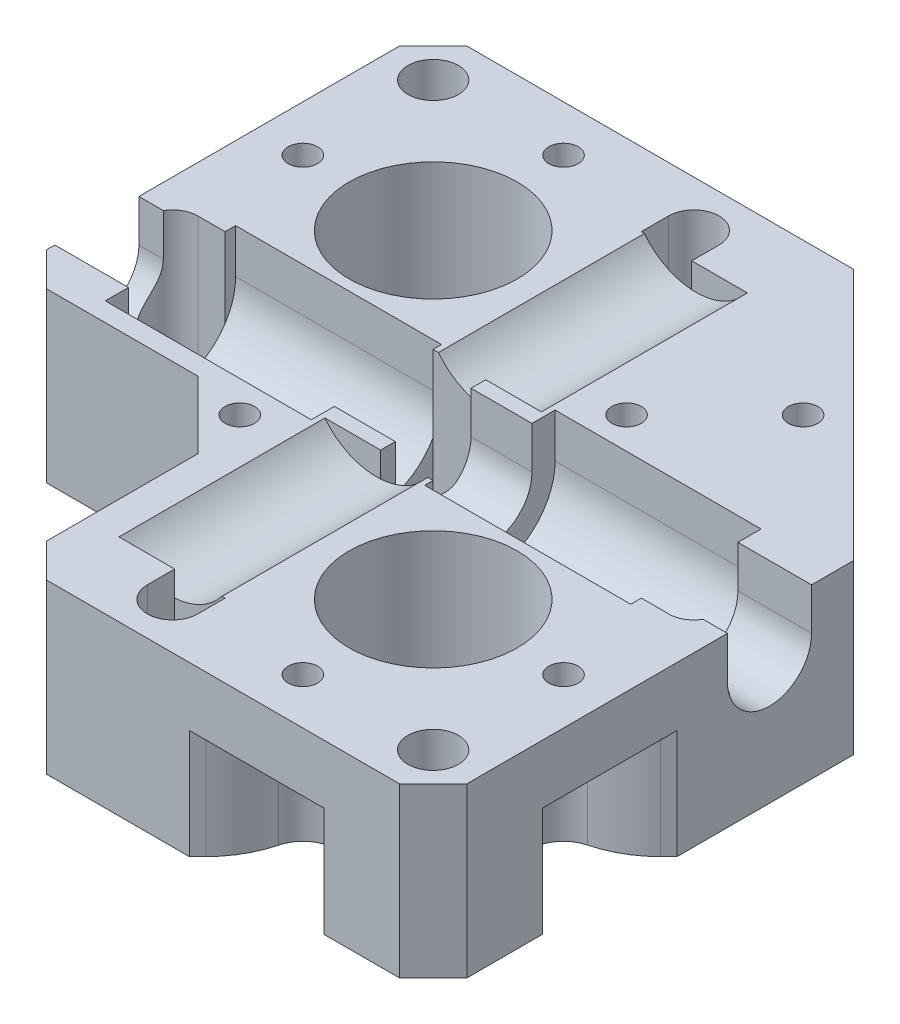
SolidWorks part; units mm, degrees
ref_plane "Front Plane" through (0, 0, 0) normal (0, 0, 1) x (1, 0, 0)
ref_plane "Top Plane" through (0, 0, 0) normal (0, 1, 0) x (1, 0, 0)
ref_plane "Right Plane" through (0, 0, 0) normal (1, 0, 0) x (0, 0, -1)
sketch "Sketch1" plane through (0, 0, 0) normal (0, 1, 0) x (1, 0, 0)
  line L1 (-40, -40) -> (40, -40)
  line L2 (-40, -40) -> (-40, 40)
  line L3 (-40, 40) -> (40, 40)
  line L4 (40, -40) -> (40, 40)
  line L5 (-40, -40) -> (40, 40) construction
  line L6 (-40, 40) -> (40, -40) construction
  point P0 (0, 0)
  dimension "D1" = 80
  dimension "D2" = 80
extrude "Boss-Extrude1" add sketch "Sketch1" against normal blind 20
sketch "Sketch2" plane through (0, 0, 0) normal (0, 1, 0) x (1, 0, 0)
  circle A0 centre (-11.5, -11.5) radius 1.75
  circle A1 centre (11.5, 11.5) radius 1.75
  circle A2 centre (22, 22) radius 1.75
  circle A3 centre (19, -34.5) radius 1.75
  circle A4 centre (34.5, -19) radius 1.75
  circle A5 centre (-34.5, 19) radius 1.75
  circle A6 centre (-19, 34.5) radius 1.75
  dimension "D1" = 3.5
  dimension "D2" = 3.5
  dimension "D3" = 3.5
  dimension "D4" = 3.5
  dimension "D5" = 3.5
  dimension "D6" = 3.5
  dimension "D7" = 3.5
  dimension "D8" = 11.5
  dimension "D9" = 11.5
  dimension "D10" = 11.5
  dimension "D11" = 11.5
  dimension "D12" = 22
  dimension "D13" = 22
  dimension "D14" = 34.5
  dimension "D15" = 34.5
  dimension "D16" = 19
  dimension "D17" = 19
  dimension "D18" = 34.5
  dimension "D19" = 19
  dimension "D20" = 19
  dimension "D21" = 34.5
extrude "Cut-Extrude1" cut sketch "Sketch2" against normal through all both and the other way through all
sketch "Sketch3" plane through (0, 0, 0) normal (0, 1, 0) x (1, 0, 0)
  line L1 (31.25, -7.75) -> (6.75, -7.75)
  line L2 (31.25, -7.75) -> (31.25, 7.75)
  line L3 (31.25, 7.75) -> (6.75, 7.75)
  line L4 (6.75, -7.75) -> (6.75, 7.75)
  line L5 (31.25, -7.75) -> (6.75, 7.75) construction
  line L6 (31.25, 7.75) -> (6.75, -7.75) construction
  line L7 (-6.75, -7.75) -> (-31.25, -7.75)
  line L8 (-6.75, -7.75) -> (-6.75, 7.75)
  line L9 (-6.75, 7.75) -> (-31.25, 7.75)
  line L10 (-31.25, -7.75) -> (-31.25, 7.75)
  line L11 (-6.75, -7.75) -> (-31.25, 7.75) construction
  line L12 (-6.75, 7.75) -> (-31.25, -7.75) construction
  point P0 (19, 0)
  point P5 (-19, 0)
  point P10 (0, 0)
  dimension "D1" = 15.5
  dimension "D2" = 0
  dimension "D3" = 24.5
  dimension "D4" = 19
  dimension "D5" = 24.5
  dimension "D6" = 15.5
  dimension "D7" = 0
  dimension "D8" = 19
extrude "Cut-Extrude2" cut sketch "Sketch3" against normal blind 13
fillet "Fillet1" radius 7.75 4 edges at (19, -13, 7.75) (19, -13, -7.75) (-19, -13, 7.75) (-19, -13, -7.75)
sketch "Sketch4" plane through (0, 0, 0) normal (0, 1, 0) x (1, 0, 0)
  line L1 (-7.75, -31.25) -> (7.75, -31.25)
  line L2 (-7.75, -31.25) -> (-7.75, -6.75)
  line L3 (-7.75, -6.75) -> (7.75, -6.75)
  line L4 (7.75, -31.25) -> (7.75, -6.75)
  line L5 (-7.75, -31.25) -> (7.75, -6.75) construction
  line L6 (-7.75, -6.75) -> (7.75, -31.25) construction
  line L7 (-7.75, 6.75) -> (7.75, 6.75)
  line L8 (-7.75, 6.75) -> (-7.75, 31.25)
  line L9 (-7.75, 31.25) -> (7.75, 31.25)
  line L10 (7.75, 6.75) -> (7.75, 31.25)
  point P0 (0, -19)
  dimension "D1" = 15.5
  dimension "D2" = 0
  dimension "D3" = 24.5
  dimension "D4" = 19
  dimension "D5" = 24.5
  dimension "D6" = 6.75
  dimension "D7" = 15.5
  dimension "D8" = 7.75
extrude "Cut-Extrude3" cut sketch "Sketch4" against normal blind 3
sketch3d "3DSketch1" [suppressed]
  line L1 (-8, -3, 8) -> (8, -3, 8)
  line L2 (-8, -3, 8) -> (-8, 0, 8)
  line L3 (-8, 0, 8) -> (8, 0, 8)
  line L4 (8, -3, 8) -> (8, 0, 8)
  circle A0 centre (0, 5, 8) radius 8
  point P2 (0, 5, 16)
  point P3 (0, 0, 8)
  point P5 (0, 0, 8)
  dimension "D4" = 16
  dimension "D1" = 8
  dimension "D2" = 0
  dimension "D3" = 5
sketch "Sketch5" plane through (0, 0, 31.25) normal (0, 0, -1) x (-1, 0, 0)
  line L0 (7.75, -3) -> (-7.75, -3) construction
  line L5 (7.75, 0) -> (-7.75, 0)
  line L6 (-7.75, 0) -> (-7.75, -3)
  line L7 (-7.75, -3) -> (7.75, -3)
  line L8 (7.75, -3) -> (7.75, 0)
  line L9 (7.75, 0) -> (-7.75, 0)
  line L10 (-7.75, 0) -> (-7.75, -3)
  line L11 (-7.75, -3) -> (7.75, -3)
  line L12 (7.75, -3) -> (7.75, 0)
  circle A0 centre (0, 4.75) radius 7.75
  line M6 (7.75, 0) -> (-7.75, 0)
  line M7 (-7.75, 0) -> (-7.75, -3)
  line M8 (-7.75, -3) -> (7.75, -3)
  line M9 (7.75, -3) -> (7.75, 0)
  dimension "D2" = 15.5
  dimension "D1" = 7.75
  dimension "D3" = 0
extrude "Boss-Extrude2" add sketch "Sketch5" along normal blind 23.5 contours A0 M6 M7 M8 | A0 L11 M9 M6 region at (-5.7238, -1.841, 31.25) region at (5.7238, -1.841, 31.25)
mirror "Mirror1" about plane through (0, 0, 0) normal (0, 0, 1) of "Boss-Extrude2"
sketch "Sketch6" plane through (0, 0, 0) normal (1, 0, 0) x (0, 0, -1)
  line L1 (5, -5) -> (-5, -5)
  line L2 (5, -5) -> (5, 0)
  line L3 (5, 0) -> (-5, 0)
  line L4 (-5, -5) -> (-5, 0)
  circle A0 centre (0, -5) radius 5
  dimension "D2" = 10
  dimension "D1" = 5
extrude "Cut-Extrude4" cut sketch "Sketch6" against normal through all both and the other way through all contours L1 A0 | A0 L3 L4 | A0 L2 L3 | L1 A0 region at (0, -7.1221, 0) region at (0, -1.1168, -3.8832) region at (0, -2.8779, 0) region at (0, -1.1168, 3.8832)
sketch "Sketch7" plane through (0, 0, 0) normal (0, 1, 0) x (1, 0, 0)
  circle A0 centre (19, -19) radius 10
  circle A1 centre (-19, 19) radius 10
  dimension "D5" = 20
  dimension "D6" = 20
  dimension "D1" = 19
  dimension "D2" = 19
  dimension "D3" = 19
  dimension "D4" = 19
extrude "Cut-Extrude5" cut sketch "Sketch7" against normal through all both and the other way through all
sketch "Sketch8" plane through (0, 0, -6.75) normal (0, 0, -1) x (-1, 0, 0)
  line L4 (6.75, 0) -> (-6.75, 0)
  line L5 (-6.75, 0) -> (-6.75, -3)
  line L6 (-6.75, -3) -> (6.75, -3)
  line L7 (6.75, -3) -> (6.75, 0)
  line L8 (6.75, 0) -> (-6.75, 0)
  line L9 (-6.75, 0) -> (-6.75, -3)
  line L10 (-6.75, -3) -> (6.75, -3)
  line L11 (6.75, -3) -> (6.75, 0)
  arc A0 (0, -3) -> (6.1237, 0) centre (0, 4.75) ccw construction
  arc A1 (-6.1237, 0) -> (0, -3) centre (0, 4.75) ccw construction
  arc A2 (0, -3) -> (6.1237, 0) centre (0, 4.75) ccw
  arc A3 (-6.1237, 0) -> (0, -3) centre (0, 4.75) ccw
  line M5 (6.75, 0) -> (-6.75, 0)
  line M6 (-6.75, 0) -> (-6.75, -3)
  line M7 (-6.75, -3) -> (6.75, -3)
  line M8 (6.75, -3) -> (6.75, 0)
  dimension "D1" = 0
extrude "Boss-Extrude3" add sketch "Sketch8" along normal blind 1.5 contours A3 M5 M6 M7 | A2 L10 M8 M5 region at (-5.1079, -1.9786, -6.75) region at (5.1079, -1.9786, -6.75)
mirror "Mirror2" about plane through (0, 0, 0) normal (0, 0, 1) of "Boss-Extrude3"
sketch "Sketch9" plane through (0, 0, 0) normal (0, 1, 0) x (1, 0, 0)
  line L0 (-10, -18) -> (-18, -10)
  line L1 (-40, -40) -> (-10, -40)
  line L2 (-40, -40) -> (-40, -10)
  line L3 (-40, -10) -> (-10, -10)
  line L4 (-10, -40) -> (-10, -10)
  line L5 (-10, -10) -> (-18, -10)
  line L6 (-10, -10) -> (-10, -18)
  line L7 (-10, -18) -> (-18, -18)
  line L8 (-18, -10) -> (-18, -18)
  dimension "D1" = 30
  dimension "D2" = 30
  dimension "D3" = 8
  dimension "D4" = 8
extrude "Cut-Extrude6" cut sketch "Sketch9" against normal through all both and the other way through all contours L0 L8 L7 | L8 L3 L2 L1 L4 L7 region at (-15.3333, 0, 15.3333) region at (-25.8421, 0, 25.8421)
chamfer "Chamfer1" distance 4 angle 45 4 edges at (40, -10, 40) (-40, -10, -40) (-40, -10, 10) (-10, -10, 40)
chamfer "Chamfer2" distance 30 angle 45 1 edges at (40, -10, -40)
sketch "Sketch10" plane through (0, 0, 0) normal (0, 1, 0) x (1, 0, 0)
  circle A0 centre (3.5, -3.5) radius 1.75
  circle A1 centre (-3.5, 3.5) radius 1.75
  circle A2 centre (34.5, -3.5) radius 1.75
  circle A3 centre (3.5, -34.5) radius 1.75
  circle A4 centre (34.5, -34.5) radius 1.75
  circle A5 centre (-3.5, 34.5) radius 1.75
  circle A6 centre (-34.5, 3.5) radius 1.75
  circle A7 centre (-34.5, 34.5) radius 1.75
  dimension "D5" = 3.5
  dimension "D6" = 3.5
  dimension "D8" = 3.5
  dimension "D10" = 3.5
  dimension "D11" = 3.5
  dimension "D12" = 3.5
  dimension "D13" = 3.5
  dimension "D16" = 3.5
  dimension "D1" = 3.5
  dimension "D2" = 3.5
  dimension "D3" = 3.5
  dimension "D4" = 3.5
  dimension "D7" = 31
  dimension "D9" = 31
  dimension "D14" = 31
  dimension "D15" = 31
extrude "Cut-Extrude7" cut sketch "Sketch10" against normal through all both and the other way through all
sketch "Sketch11" plane through (0, 0, 0) normal (0, 1, 0) x (1, 0, 0)
  line L0 (-6.75, 5) -> (-6.75, 7.75) construction
  line L1 (-0.5, 3.5) -> (-6.75, 3.5)
  line L2 (-0.5, 3.5) -> (-0.5, 6.375)
  line L3 (-0.5, 6.375) -> (-6.75, 6.375)
  line L4 (-6.75, 3.5) -> (-6.75, 6.375)
  line L5 (6.75, -5) -> (6.75, -7.75) construction
  line L6 (0.5, -3.5) -> (6.75, -3.5)
  line L7 (0.5, -3.5) -> (0.5, -6.375)
  line L8 (0.5, -6.375) -> (6.75, -6.375)
  line L9 (6.75, -3.5) -> (6.75, -6.375)
  line L10 (31.25, -7.75) -> (31.25, -5) construction
  line L11 (34.5, -0.5) -> (31.25, -0.5)
  line L12 (34.5, -0.5) -> (34.5, -6.375)
  line L13 (34.5, -6.375) -> (31.25, -6.375)
  line L14 (31.25, -0.5) -> (31.25, -6.375)
  line L15 (-6.1237, -31.25) -> (6.1237, -31.25) construction
  line L16 (-34.5, 6.5) -> (-31.25, 6.5)
  line L17 (-34.5, 6.5) -> (-34.5, 0.5)
  line L18 (-34.5, 0.5) -> (-31.25, 0.5)
  line L19 (-31.25, 6.5) -> (-31.25, 0.5)
  line L20 (3.5, -0.5) -> (6.75, -0.5)
  line L21 (3.5, -0.5) -> (3.5, -6.375)
  line L22 (3.5, -6.375) -> (6.75, -6.375)
  line L23 (6.75, -0.5) -> (6.75, -6.375)
  line L24 (-3.5, 0.5) -> (-6.75, 0.5)
  line L25 (-3.5, 0.5) -> (-3.5, 6.375)
  line L26 (-3.5, 6.375) -> (-6.75, 6.375)
  line L27 (-6.75, 0.5) -> (-6.75, 6.375)
  line L32 (0.5, -31.25) -> (6.5, -31.25)
  line L33 (0.5, -31.25) -> (0.5, -34.5)
  line L34 (0.5, -34.5) -> (6.5, -34.5)
  line L35 (6.5, -31.25) -> (6.5, -34.5)
  line L36 (-31.25, 7.75) -> (-31.25, 5) construction
  line L37 (-0.4632, 34.5) -> (-6.4632, 34.5)
  line L38 (-0.4632, 34.5) -> (-0.4632, 31.25)
  line L39 (-0.4632, 31.25) -> (-6.4632, 31.25)
  line L40 (-6.4632, 34.5) -> (-6.4632, 31.25)
  line L41 (6.1237, 31.25) -> (-6.1237, 31.25) construction
  circle A0 centre (-34.5, 3.5) radius 1.75 construction
  circle A1 centre (34.5, -3.5) radius 1.75 construction
  circle A2 centre (-3.5, 3.5) radius 1.75 construction
  circle A3 centre (3.5, -3.5) radius 1.75 construction
  circle A4 centre (-34.5, 3.5) radius 1.75
  circle A5 centre (34.5, -3.5) radius 1.75
  circle A6 centre (-3.5, 3.5) radius 1.75
  circle A7 centre (3.5, -3.5) radius 1.75
  circle A8 centre (-3.5, 3.5) radius 3
  circle A9 centre (3.5, -3.5) radius 3
  circle A10 centre (34.5, -3.5) radius 3
  circle A11 centre (-34.5, 3.5) radius 3
  circle A12 centre (-3.5, 34.5) radius 1.75 construction
  circle A13 centre (3.5, -34.5) radius 1.75 construction
  circle A14 centre (-3.5, 34.5) radius 1.75
  circle A15 centre (3.5, -34.5) radius 1.75
  circle A16 centre (3.5, -34.5) radius 3
  circle A17 centre (-3.5, 34.5) radius 3.0368
  dimension "D1" = 6
  dimension "D2" = 6
  dimension "D3" = 6
  dimension "D4" = 6
  dimension "D5" = 0
  dimension "D6" = 0
extrude "Cut-Extrude11" [suppressed] cut sketch "Sketch11" against normal blind 17 contours A17 | L40 L39 L38 L37 | L4 L1 L2 L3 | L26 L25 L24 L27 | A8 | A9 | L9 L6 L7 L8 | L22 L21 L20 L23 | L11 L14 L13 L12 | A10 | A11 | L16 L19 L18 L17 | A16 | L35 L34 L33 L32
sketch "Sketch12" plane through (0, 0, 0) normal (0, 1, 0) x (1, 0, 0)
  circle A0 centre (-34.5, 34.5) radius 1.75 construction
  circle A1 centre (34.5, -34.5) radius 1.75 construction
  circle A2 centre (-34.5, 34.5) radius 1.75
  circle A3 centre (34.5, -34.5) radius 1.75
  circle A4 centre (34.5, -34.5) radius 3
  circle A5 centre (-34.5, 34.5) radius 3
  dimension "D1" = 6
  dimension "D2" = 6
extrude "Cut-Extrude12" cut sketch "Sketch12" against normal blind 8
sketch "Sketch13" plane through (0, -20, 0) normal (0, -1, 0) x (1, 0, 0)
  circle A0 centre (-19, -19) radius 10 construction
  circle A1 centre (19, 19) radius 10 construction
  circle A2 centre (-19, -19) radius 10
  circle A3 centre (19, 19) radius 10
  circle A4 centre (19, 19) radius 11
  circle A5 centre (-19, -19) radius 11
  dimension "D1" = 22
  dimension "D2" = 22
extrude "Cut-Extrude13" cut sketch "Sketch13" against normal blind 3
sketch "Sketch14" plane through (0, -20, 0) normal (0, -1, 0) x (1, 0, 0)
  line L1 (-34.5, -15.8246) -> (-37.25, -17.4123)
  line L2 (-37.25, -17.4123) -> (-37.25, -20.5877)
  line L3 (-37.25, -20.5877) -> (-34.5, -22.1754)
  line L4 (-34.5, -22.1754) -> (-31.75, -20.5877)
  line L5 (-31.75, -20.5877) -> (-31.75, -17.4123)
  line L6 (-31.75, -17.4123) -> (-34.5, -15.8246)
  line L7 (-15.8246, -34.5) -> (-17.4123, -31.75)
  line L8 (-17.4123, -31.75) -> (-20.5877, -31.75)
  line L9 (-20.5877, -31.75) -> (-22.1754, -34.5)
  line L10 (-22.1754, -34.5) -> (-20.5877, -37.25)
  line L11 (-20.5877, -37.25) -> (-17.4123, -37.25)
  line L12 (-17.4123, -37.25) -> (-15.8246, -34.5)
  line L13 (34.5, 22.1754) -> (31.75, 20.5877)
  line L14 (31.75, 20.5877) -> (31.75, 17.4123)
  line L15 (31.75, 17.4123) -> (34.5, 15.8246)
  line L16 (34.5, 15.8246) -> (37.25, 17.4123)
  line L17 (37.25, 17.4123) -> (37.25, 20.5877)
  line L18 (37.25, 20.5877) -> (34.5, 22.1754)
  line L19 (22.1754, 34.5) -> (20.5877, 37.25)
  line L20 (20.5877, 37.25) -> (17.4123, 37.25)
  line L21 (17.4123, 37.25) -> (15.8246, 34.5)
  line L22 (15.8246, 34.5) -> (17.4123, 31.75)
  line L23 (17.4123, 31.75) -> (20.5877, 31.75)
  line L24 (20.5877, 31.75) -> (22.1754, 34.5)
  line L25 (-8.3246, 11.5) -> (-9.9123, 14.25)
  line L26 (-9.9123, 14.25) -> (-13.0877, 14.25)
  line L27 (-13.0877, 14.25) -> (-14.6754, 11.5)
  line L28 (-14.6754, 11.5) -> (-13.0877, 8.75)
  line L29 (-13.0877, 8.75) -> (-9.9123, 8.75)
  line L30 (-9.9123, 8.75) -> (-8.3246, 11.5)
  line L31 (8.3246, -11.5) -> (9.9123, -14.25)
  line L32 (9.9123, -14.25) -> (13.0877, -14.25)
  line L33 (13.0877, -14.25) -> (14.6754, -11.5)
  line L34 (14.6754, -11.5) -> (13.0877, -8.75)
  line L35 (13.0877, -8.75) -> (9.9123, -8.75)
  line L36 (9.9123, -8.75) -> (8.3246, -11.5)
  line L37 (22, -18.8246) -> (19.25, -20.4123)
  line L38 (19.25, -20.4123) -> (19.25, -23.5877)
  line L39 (19.25, -23.5877) -> (22, -25.1754)
  line L40 (22, -25.1754) -> (24.75, -23.5877)
  line L41 (24.75, -23.5877) -> (24.75, -20.4123)
  line L42 (24.75, -20.4123) -> (22, -18.8246)
  circle A0 centre (19, 34.5) radius 1.75 construction
  circle A1 centre (34.5, 19) radius 1.75 construction
  circle A2 centre (-34.5, -19) radius 1.75 construction
  circle A3 centre (22, -22) radius 1.75 construction
  circle A4 centre (11.5, -11.5) radius 1.75 construction
  circle A5 centre (-19, -34.5) radius 1.75 construction
  circle A6 centre (-11.5, 11.5) radius 1.75 construction
  circle A7 centre (19, 34.5) radius 1.75
  circle A8 centre (34.5, 19) radius 1.75
  circle A9 centre (-34.5, -19) radius 1.75
  circle A10 centre (22, -22) radius 1.75
  circle A11 centre (11.5, -11.5) radius 1.75
  circle A12 centre (-19, -34.5) radius 1.75
  circle A13 centre (-11.5, 11.5) radius 1.75
  circle A14 centre (-34.5, -19) radius 2.75 construction
  circle A15 centre (-19, -34.5) radius 2.75 construction
  circle A16 centre (34.5, 19) radius 2.75 construction
  circle A17 centre (19, 34.5) radius 2.75 construction
  circle A18 centre (-11.5, 11.5) radius 2.75 construction
  circle A19 centre (11.5, -11.5) radius 2.75 construction
  circle A20 centre (22, -22) radius 2.75 construction
  point P21 (37.25, 19)
  point P50 (-37.25, -19)
  point P51 (-19, -37.25)
  point P52 (11.5, -8.75)
  dimension "D1" = 5.5
  dimension "D2" = 5.5
  dimension "D3" = 5.5
  dimension "D4" = 5.5
  dimension "D5" = 5.5
  dimension "D6" = 5.5
  dimension "D7" = 5.5
extrude "Cut-Extrude14" cut sketch "Sketch14" against normal blind 16
sketch "Sketch15" plane through (0, -20, 0) normal (0, -1, 0) x (1, 0, 0)
  line L0 (10, -40) -> (-36, -40) construction
  line L1 (-23, -34.5) -> (-15, -34.5)
  line L2 (-23, -34.5) -> (-23, -40)
  line L3 (-23, -40) -> (-15, -40)
  line L4 (-15, -34.5) -> (-15, -40)
  line L5 (-40, -36) -> (-40, 6) construction
  line L6 (-34.5, -23) -> (-40, -23)
  line L7 (-34.5, -23) -> (-34.5, -15)
  line L8 (-34.5, -15) -> (-40, -15)
  line L9 (-40, -23) -> (-40, -15)
  line L10 (-6, 40) -> (36, 40) construction
  line L11 (15, 34.5) -> (23, 34.5)
  line L12 (15, 34.5) -> (15, 40)
  line L13 (15, 40) -> (23, 40)
  line L14 (23, 34.5) -> (23, 40)
  line L15 (40, 36) -> (40, -10) construction
  line L16 (34.5, 15) -> (40, 15)
  line L17 (34.5, 15) -> (34.5, 23)
  line L18 (34.5, 23) -> (40, 23)
  line L19 (40, 15) -> (40, 23)
  line L20 (-13.0877, 8.75) -> (-18, 10)
  line L21 (-18, 10) -> (-10, 18)
  line L22 (-10, 18) -> (-8.3246, 11.5)
  line L23 (-8.3246, 11.5) -> (-13.0877, 8.75)
  line L24 (13.0877, -8.75) -> (40, -10)
  line L25 (10, -40) -> (9.9123, -14.25)
  line L26 (9.9123, -14.25) -> (13.0877, -8.75)
  line L27 (10, -40) -> (40, -10)
  circle A0 centre (-11.5, 11.5) radius 1.75 construction
  circle A1 centre (-34.5, -19) radius 1.75 construction
  circle A2 centre (-19, -34.5) radius 1.75 construction
  circle A3 centre (22, -22) radius 1.75 construction
  circle A4 centre (11.5, -11.5) radius 1.75 construction
  circle A5 centre (34.5, 19) radius 1.75 construction
  circle A6 centre (19, 34.5) radius 1.75 construction
  circle A7 centre (-11.5, 11.5) radius 1.75
  circle A8 centre (-34.5, -19) radius 1.75
  circle A9 centre (-19, -34.5) radius 1.75
  circle A10 centre (22, -22) radius 1.75
  circle A11 centre (11.5, -11.5) radius 1.75
  circle A12 centre (34.5, 19) radius 1.75
  circle A13 centre (19, 34.5) radius 1.75
  circle A14 centre (-34.5, -19) radius 4
  circle A15 centre (-19, -34.5) radius 4
  circle A16 centre (34.5, 19) radius 4
  circle A17 centre (19, 34.5) radius 4
  dimension "D1" = 8
  dimension "D2" = 8
  dimension "D3" = 8
  dimension "D4" = 8
extrude "Cut-Extrude15" cut sketch "Sketch15" against normal blind 13 contours A11 L26 L25 L27 L24 A10 | L2 L3 L4 L1 | A15 | A14 | L8 L9 L6 L7 | L21 L22 L23 L20 | A16 | L18 L19 L16 L17 | A17 | L14 L13 L12 L11 region at (20.1853, -20, -19.7439)
chamfer "Chamfer3" distance 4 angle 45 8 edges at (40, -13.5, 23) (40, -13.5, 15) (15, -13.5, 40) (23, -13.5, 40) (-15, -13.5, -40) (-23, -13.5, -40) (-40, -13.5, -15) (-40, -13.5, -23)
fillet "Fillet2" radius 12 8 edges at (15, -13.5, 36) (23, -13.5, 36) (36, -13.5, 23) (36, -13.5, 15) (-23, -13.5, -36) (-15, -13.5, -36) (-36, -13.5, -23) (-36, -13.5, -15)
sketch "Sketch19" plane through (0, 0, 0) normal (0, 1, 0) x (1, 0, 0)
  line L0 (-6.1237, 6.75) -> (6.1237, 6.75) construction
  line L1 (-6.5, 3.5) -> (-0.5, 3.5)
  line L2 (-6.5, 3.5) -> (-6.5, 6.75)
  line L3 (-6.5, 6.75) -> (-0.5, 6.75)
  line L4 (-0.5, 3.5) -> (-0.5, 6.75)
  line L5 (-31.25, 7.75) -> (-31.25, 5) construction
  line L6 (-34.5, 0.5) -> (-31.25, 0.5)
  line L7 (-34.5, 0.5) -> (-34.5, 6.5)
  line L8 (-34.5, 6.5) -> (-31.25, 6.5)
  line L9 (-31.25, 0.5) -> (-31.25, 6.5)
  line L10 (6.1237, -6.75) -> (-6.1237, -6.75) construction
  line L11 (6.5, -3.5) -> (0.5, -3.5)
  line L12 (6.5, -3.5) -> (6.5, -6.75)
  line L13 (6.5, -6.75) -> (0.5, -6.75)
  line L14 (0.5, -3.5) -> (0.5, -6.75)
  line L15 (-6.1237, -31.25) -> (6.1237, -31.25) construction
  line L16 (6.5, -34.5) -> (0.5, -34.5)
  line L17 (6.5, -34.5) -> (6.5, -31.25)
  line L18 (6.5, -31.25) -> (0.5, -31.25)
  line L19 (0.5, -34.5) -> (0.5, -31.25)
  line L20 (6.1237, 31.25) -> (-6.1237, 31.25) construction
  line L21 (-6.5, 34.5) -> (-0.5, 34.5)
  line L22 (-6.5, 34.5) -> (-6.5, 31.25)
  line L23 (-6.5, 31.25) -> (-0.5, 31.25)
  line L24 (-0.5, 34.5) -> (-0.5, 31.25)
  line L25 (31.25, -7.75) -> (31.25, -5) construction
  line L26 (34.5, -0.5) -> (31.25, -0.5)
  line L27 (34.5, -0.5) -> (34.5, -6.4875)
  line L28 (34.5, -6.4875) -> (31.25, -6.4875)
  line L29 (31.25, -0.5) -> (31.25, -6.4875)
  line L30 (-6.75, 5) -> (-6.75, 7.75) construction
  line L31 (-3.5, 0.5) -> (-6.75, 0.5)
  line L32 (-3.5, 0.5) -> (-3.5, 6.75)
  line L33 (-3.5, 6.75) -> (-6.75, 6.75)
  line L34 (-6.75, 0.5) -> (-6.75, 6.75)
  line L35 (6.75, -5) -> (6.75, -7.75) construction
  line L36 (3.5, -0.5) -> (6.75, -0.5)
  line L37 (3.5, -0.5) -> (3.5, -6.75)
  line L38 (3.5, -6.75) -> (6.75, -6.75)
  line L39 (6.75, -0.5) -> (6.75, -6.75)
  circle A0 centre (34.5, -3.5) radius 1.75 construction
  circle A1 centre (-3.5, 34.5) radius 1.75 construction
  circle A2 centre (-34.5, 3.5) radius 1.75 construction
  circle A3 centre (-3.5, 3.5) radius 1.75 construction
  circle A4 centre (3.5, -3.5) radius 1.75 construction
  circle A5 centre (3.5, -34.5) radius 1.75 construction
  circle A6 centre (34.5, -3.5) radius 1.75
  circle A7 centre (-3.5, 34.5) radius 1.75
  circle A8 centre (-34.5, 3.5) radius 1.75
  circle A9 centre (-3.5, 3.5) radius 1.75
  circle A10 centre (3.5, -3.5) radius 1.75
  circle A11 centre (3.5, -34.5) radius 1.75
  circle A12 centre (-3.5, 3.5) radius 3
  circle A13 centre (3.5, -3.5) radius 3
  circle A14 centre (3.5, -34.5) radius 3
  circle A15 centre (-3.5, 34.5) radius 3
  circle A16 centre (-34.5, 3.5) radius 3
  circle A17 centre (34.5, -3.5) radius 3
  dimension "D1" = 6
  dimension "D2" = 6
  dimension "D3" = 6
  dimension "D4" = 6
  dimension "D5" = 6
  dimension "D6" = 6
extrude "Cut-Extrude19" cut sketch "Sketch19" against normal blind 17 contours L37 A13 L11 A10 | A13 L37 L13 L12 | A13 L14 L13 L37 | L32 A12 L1 A9 | L1 A12 L32 A9 | A12 L2 L33 L34 L31 | A12 L32 L3 L2 | L1 A12 L32 A9 | L32 A12 L1 A9 | A12 L4 L3 L32 | L37 A13 L11 A10 | L11 A13 L37 A10 | A13 L12 L38 L39 L36 | L28 A17 L27 A6 | L27 A17 L28 A6 | A17 L26 L29 L28 | L11 A13 L37 A10 | L16 A14 A11 | L16 A14 A11 | A14 L17 L18 L19 | A15 L22 L23 L24 | L21 A15 A7 | L21 A15 A7 | A16 L6 L9 L8 | L7 A16 A8 | L7 A16 A8 | A13 | A12 | A10 region at (-1.9531, 0, -5.0469) region at (-1.9531, 0, -1.9531) region at (-1.4022, 0, -6.0523) region at (-5.0469, 0, -5.0469) region at (-5.0469, 0, -1.9531) region at (-5.125, 0, -0.5704) region at (-5.5978, 0, -6.0523) region at (-32.3304, 0, -1.3304) region at (-37.4329, 0, -3.5) region at (-34.4329, 0, -1.125) region at (5.0469, 0, 5.0469) region at (5.6711, 0, 1.3289) region at (5.0469, 0, 1.9531) region at (5.5978, 0, 6.0523) region at (1.9531, 0, 1.9531) region at (1.9531, 0, 5.0469) region at (1.4022, 0, 6.0523) region at (3.5, 0, 37.4329) region at (3.5, 0, 31.4318) region at (5.875, 0, 34.4329) region at (-3.5, 0, -36.3171) region at (-1.125, 0, -34.4329) region at (-0.5682, 0, -32.875) region at (31.4351, 0, 3.3602) region at (36.573, 0, 1.427) region at (34.433, 0, 1.125)
